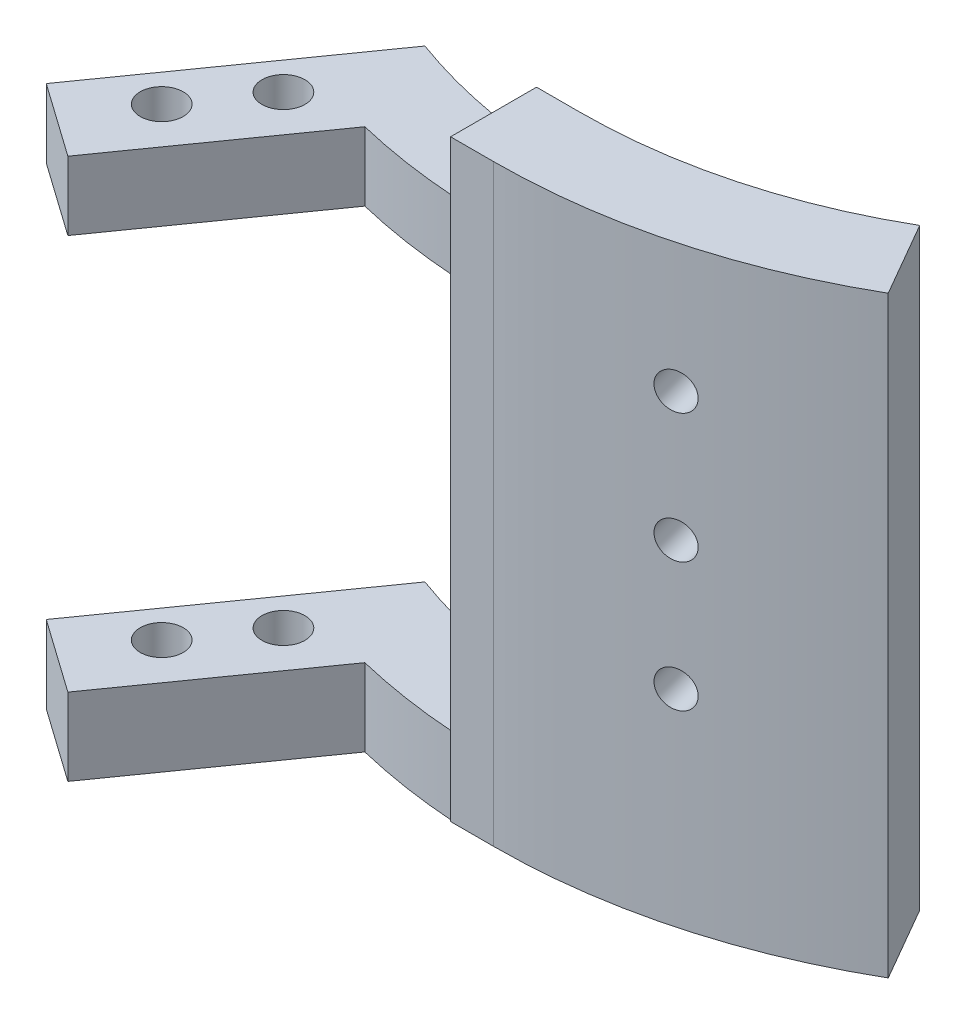
SolidWorks part; units mm, degrees
ref_plane "Front Plane" through (0, 0, 0) normal (0, 0, 1) x (1, 0, 0)
ref_plane "Top Plane" through (0, 0, 0) normal (0, 1, 0) x (1, 0, 0)
ref_plane "Right Plane" through (0, 0, 0) normal (1, 0, 0) x (0, 0, -1)
sketch "Sketch1" plane through (0, 0, 0) normal (0, 0, 1) x (1, 0, 0)
  line L0 (-25, 30) -> (25, 30)
  line L1 (-20, 25) -> (20, 25)
  line L3 (-20, -25) -> (20, -25)
  line L4 (20, 25) -> (20, -25)
  line L5 (-20, 25) -> (20, -25) construction
  line L6 (-20, -25) -> (20, 25) construction
  line L7 (25, 30) -> (25, -30)
  line L8 (-25, -30) -> (25, -30)
  line L9 (-25, 30) -> (-25, 25)
  line L10 (-20, 25) -> (-25, 25)
  line L11 (-20, -25) -> (-25, -25)
  line L12 (-25, -25) -> (-25, -30)
  line L13 (-25, 30) -> (-25, -30) construction
  line L14 (-20, 25) -> (-20, -25) construction
  point P0 (0, 0)
  dimension "D1" = 40
  dimension "D2" = 50
  dimension "D3" = 5
extrude "Boss-Extrude2" add sketch "Sketch1" along normal blind 20
fillet "Fillet1" 2 edges at (-25, 27.5, 20) (-25, 27.5, 0) type full round first side face at (-1.25, 0, 20) second side face at (-1.25, 0, 0) middle face at (-25, 27.5, 10)
fillet "Fillet2" 2 edges at (-25, -27.5, 20) (-25, -27.5, 0) type full round first side face at (1.25, 0, 20) second side face at (1.25, 0, 0) middle face at (-25, -27.5, 10)
sketch "Sketch5" plane through (0, 30, 0) normal (0, 1, 0) x (1, 0, 0)
  circle A0 centre (-15, -10) radius 7 construction
  circle A1 centre (-15, -3) radius 1
  circle A2 centre (-22, -10) radius 1
  circle A3 centre (-15, -17) radius 1
  circle A4 centre (-8, -10) radius 1
  circle A5 centre (-15, -10) radius 5.5
  dimension "D1" = 14
  dimension "D2" = 2
  dimension "D3" = 11
extrude "Cut-Extrude5" cut sketch "Sketch5" against normal through all
sketch "Sketch10" plane through (25, 0, 0) normal (1, 0, 0) x (0, 0, -1)
  line L1 (-15, 28.1801) -> (-15, -28.1801)
  line L3 (-20, -30) -> (-20, 30) construction
  line L4 (-10, 30) -> (-10, 19.211) construction
  line L5 (-20, 30) -> (0, 30) construction
  line L7 (-5, 28.1801) -> (-5, -28.1801)
  line L9 (0, -30) -> (0, 30) construction
  line L10 (0, -30) -> (0, 30)
  line L11 (-20, -30) -> (-20, 30)
  line L12 (-15, 28.1801) -> (-15, 30)
  line L13 (-15, 30) -> (-20, 30)
  line L14 (-15, -28.1801) -> (-15, -30)
  line L15 (-20, -30) -> (0, -30) construction
  line L16 (-15, -30) -> (-20, -30)
  line L17 (-5, -28.1801) -> (-5, -30)
  line L18 (-5, -30) -> (0, -30)
  line L19 (-5, 28.1801) -> (-5, 30)
  line L20 (-5, 30) -> (0, 30)
  dimension "D2" = 5
extrude "Cut-Extrude7" cut sketch "Sketch10" against normal blind 25
fillet "Fillet5" radius 10 4 edges at (0, 27.5, 15) (0, 27.5, 5) (0, -27.5, 15) (0, -27.5, 5)
sketch "Sketch12" plane through (0, -30, 0) normal (0, -1, 0) x (1, 0, 0)
  line L0 (56.2263, -3.3597) -> (61.2225, 5.3027)
  line L1 (25, 15) -> (25, 5)
  arc A0 (56.2263, -3.3597) -> (25, 5) centre (25, -57.5) ccw
  arc A1 (61.2225, 5.3027) -> (25, 15) centre (25, -57.5) ccw
extrude "Boss-Extrude5" add sketch "Sketch12" against normal up to surface (60 mm away) up to face at (-16, 30, 3)
ref_plane "Plane1" through (2.921, 0, 10.9109) normal (-0.2586, 0, -0.966) x (-0.966, 0, 0.2586)
sketch "Sketch13" plane through (2.921, 0, 10.9109) normal (-0.2586, 0, -0.966) x (-0.966, 0, 0.2586)
  line L0 (-39.0195, 30) -> (-39.0195, 0) construction
  line L1 (-22.8565, 30) -> (-55.1825, 30) construction
  line L2 (-39.0195, 0) -> (-39.0195, -30) construction
  line L3 (-55.1825, -30) -> (-22.8565, -30) construction
  circle A0 centre (-39.0195, 15) radius 2.1
  circle A1 centre (-39.0195, 0) radius 2.1
  circle A2 centre (-39.0195, -15) radius 2.1
  dimension "D1" = 4.2
extrude "Cut-Extrude8" cut sketch "Sketch13" against normal blind 60
ref_plane "Plane2" through (4.3924, 0, 18.6716) normal (-0.229, 0, -0.9734) x (-0.9734, 0, 0.229)
ref_plane "Plane3" through (5.1366, 0, 21.8352) normal (-0.229, 0, -0.9734) x (-0.9734, 0, 0.229)
sketch "Sketch15" plane through (0, 30, 0) normal (0, 1, 0) x (1, 0, 0)
  line L0 (8.6603, -5) -> (8.6603, -15)
  arc A0 (8.6603, -5) -> (8.6603, -15) centre (-15, -10) ccw
extrude "Cut-Extrude9" cut sketch "Sketch15" against normal blind 60
sketch "Sketch16" plane through (0, 30, 0) normal (0, 1, 0) x (1, 0, 0)
  line L0 (-6.3079, -33.2204) -> (8.6603, -15)
  line L2 (8.6603, -5) -> (3.4964, -1.3504)
  line L3 (3.4964, -1.3504) -> (-14.7906, -27.2253)
  line L4 (-53.6728, 0.2545) -> (-8.7578, -31.4889) construction
  line L5 (-14.7906, -27.2253) -> (-6.3079, -33.2204)
  line L7 (8.6603, -5) -> (20.0003, -5)
  line L9 (8.6603, -15) -> (20.0003, -15)
  line L10 (20.0003, -5) -> (20.0003, -15)
  line L11 (8.6603, -5) -> (20.0003, -15) construction
  line L12 (8.6603, -15) -> (20.0003, -5) construction
  point P12 (14.3303, -10)
  point P14 (0, 0)
  point P15 (0, 0)
  dimension "D1" = 11.34
extrude "Cut-Extrude10" cut sketch "Sketch16" against normal blind 60
sketch "Sketch17" plane through (0, 16, 0) normal (0, 1, 0) x (1, 0, 0)
  line L0 (-1.0621, -7.6052) -> (3.3607, -1.3472)
  line L1 (-1.0621, -7.6052) -> (-12.6052, -23.9379)
  line L2 (-12.6052, -23.9379) -> (-14.8826, -27.1603)
  line L3 (-53.6728, 0.2545) -> (-8.7578, -31.4889) construction
  line L4 (-14.8826, -27.1603) -> (-6.3079, -33.2204)
  line L5 (-8.7578, -31.4889) -> (-6.3079, -33.2204) construction
  line L6 (-6.3079, -33.2204) -> (7.9981, -12.9783)
  line L7 (-6.3079, -33.2204) -> (11.0067, -8.7213) construction
  line L8 (20.0003, -15) -> (20.0003, -5) construction
  line L9 (20.0003, -15) -> (20.0003, -5)
  arc A0 (3.3607, -1.3472) -> (20.0003, -5) centre (25, 57.5) ccw
  arc A1 (7.9981, -12.9783) -> (20.0003, -14.8274) centre (25, 57.5) ccw
  circle A2 centre (-0.2268, -14.2202) radius 2.5
  circle A3 centre (-6.0907, -22.5172) radius 2.5
  circle M1 centre (-6.0907, -22.5172) radius 2.5
  line M5 (-1.0621, -7.6052) -> (-12.6052, -23.9379)
  circle M8 centre (-0.2268, -14.2202) radius 2.5
  line M10 (-8.7578, -31.4889) -> (-6.3079, -33.2204)
  line M11 (-6.3079, -33.2204) -> (11.0067, -8.7213)
  line M12 (11.0067, -8.7213) -> (-38.8081, 26.485)
extrude "Boss-Extrude6" add sketch "Sketch17" along normal blind 8 contours L2 L4 L0 M10 M11 M12 M5 M1 M8 | A1 L9 A0 L0 M11 M12 region at (-1.7641, 16, 17.8798) region at (13.4225, 16, 8.4463)
sketch "Sketch18" plane through (0, -39, 0) normal (0, 1, 0) x (1, 0, 0)
  line L4 (3.3607, -1.3472) -> (-14.8826, -27.1603)
  line L5 (-14.8826, -27.1603) -> (-6.3079, -33.2204)
  line L6 (-6.3079, -33.2204) -> (7.9981, -12.9783)
  line L7 (20.0003, -14.8274) -> (20.0003, -5)
  line L8 (3.3607, -1.3472) -> (-14.8826, -27.1603)
  line L9 (-14.8826, -27.1603) -> (-6.3079, -33.2204)
  line L10 (-6.3079, -33.2204) -> (7.9981, -12.9783)
  line L12 (25, -5) -> (20.0003, -5)
  line L13 (20.0003, -5) -> (20.0003, -15)
  line L14 (20.0003, -15) -> (25, -15)
  line L15 (61.2225, -5.3027) -> (56.2263, 3.3597)
  line L16 (25, -5) -> (20.0003, -5)
  line L17 (20.0003, -14.8274) -> (20.0003, -15)
  line L18 (20.0003, -15) -> (25, -15)
  line L19 (61.2225, -5.3027) -> (56.2263, 3.3597)
  circle A0 centre (-6.0907, -22.5172) radius 2.5 construction
  circle A1 centre (-0.2268, -14.2202) radius 2.5 construction
  arc A2 (7.9981, -12.9783) -> (20.0003, -14.8274) centre (25, 57.5) ccw
  arc A3 (3.3607, -1.3472) -> (20.0003, -5) centre (25, 57.5) ccw
  arc A4 (7.9981, -12.9783) -> (20.0003, -14.8274) centre (25, 57.5) ccw
  arc A5 (3.3607, -1.3472) -> (20.0003, -5) centre (25, 57.5) ccw
  circle A6 centre (-6.0907, -22.5172) radius 2.5
  circle A7 centre (-0.2268, -14.2202) radius 2.5
  arc A10 (25, -15) -> (61.2225, -5.3027) centre (25, 57.5) ccw
  arc A11 (25, -5) -> (56.2263, 3.3597) centre (25, 57.5) ccw
  arc A12 (25, -15) -> (61.2225, -5.3027) centre (25, 57.5) ccw
  arc A13 (25, -5) -> (56.2263, 3.3597) centre (25, 57.5) ccw
  dimension "D1" = 0
  dimension "D2" = 0
extrude "Boss-Extrude7" add sketch "Sketch18" along normal up to surface (9 mm away) up to face at (34.7728, -30, 7.7299)
equation "\"éà\"=10"
